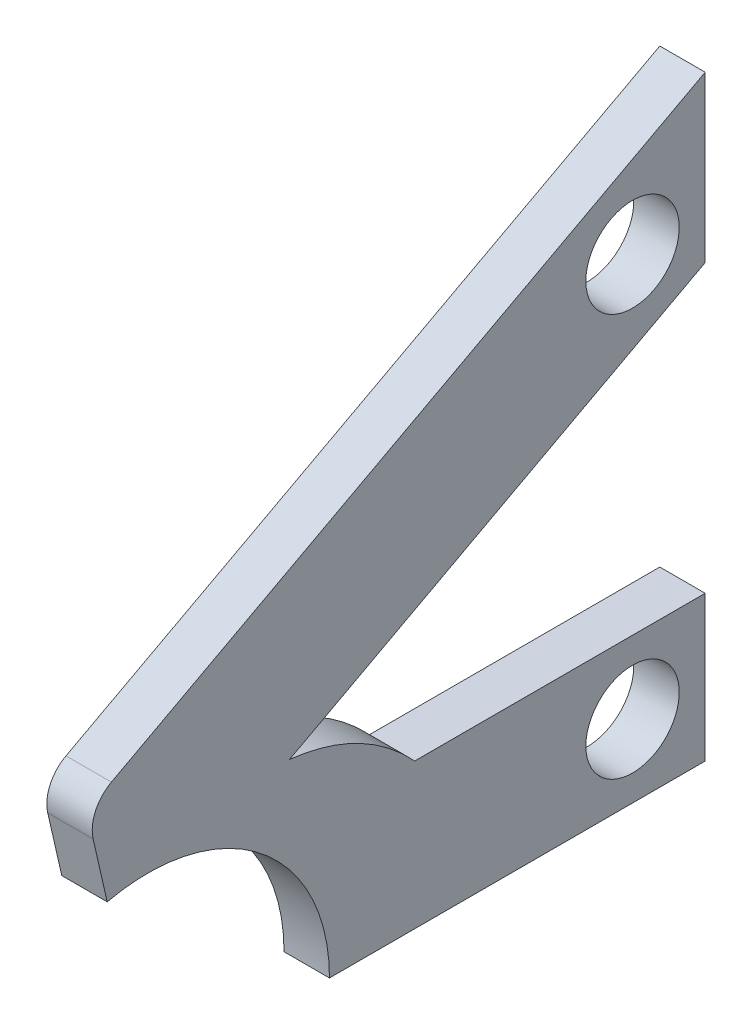
SolidWorks part; units mm, degrees
material "AISI 4130 Steel, annealed at 865C"
ref_plane "Front Plane" through (0, 0, 0) normal (0, 0, 1) x (1, 0, 0)
ref_plane "Top Plane" through (0, 0, 0) normal (0, 1, 0) x (1, 0, 0)
ref_plane "Right Plane" through (0, 0, 0) normal (1, 0, 0) x (0, 0, -1)
sketch "Sketch2" plane through (-112.555, 0, -573.5897) normal (-1, 0, 0) x (0, 0.6231, 0.7821)
  line L0 (843.7852, 138.5824) -> (864.3306, 122.2137)
  line L1 (871.0899, 172.8543) -> (811.2713, 97.7721) construction
  line L2 (864.3306, 122.2137) -> (884.1965, 122.2137) construction
  line L3 (884.1965, 122.2137) -> (887.6455, 124.9615)
  line L4 (850.1161, 146.5287) -> (866.0089, 133.8669)
  line L5 (888.3957, 127.9526) -> (869.774, 171.2026)
  line L6 (875.6249, 131.922) -> (862.593, 162.1893)
  line L7 (843.7852, 138.5824) -> (850.1161, 146.5287)
  line L8 (862.593, 162.1893) -> (869.774, 171.2026)
  line L9 (850.9238, 139.3901) -> (868.4622, 161.4036) construction
  circle A0 centre (874.2635, 114.3) radius 12.7 construction
  arc A1 (864.3306, 122.2137) -> (884.1965, 122.2137) centre (874.2635, 114.3) cw
  arc A2 (887.6455, 124.9615) -> (888.3957, 127.9526) centre (886.0628, 126.9481) ccw
  circle A3 centre (850.9238, 139.3901) radius 3.2639
  circle A4 centre (868.4622, 161.4036) radius 3.2639
  spline S0 degree 2 poles (866.0089, 133.8669) (871.1832, 134.6851) (875.6249, 131.922) knots 0 0 0 1 1 1
  point P17 (889.163, 126.1705)
  dimension "D5" = 2.54
  dimension "D6" = 6.5278
  dimension "D10" = 6.5278
  dimension "D1" = 10.16
  dimension "D2" = 10.16
  dimension "D3" = 6.35
  dimension "D4" = 20.32
  dimension "D7" = 5.08
  dimension "D8" = 5.08
  dimension "D11" = 5.08
extrude "Boss-Extrude1" add sketch "Sketch2" along normal blind 3.175
